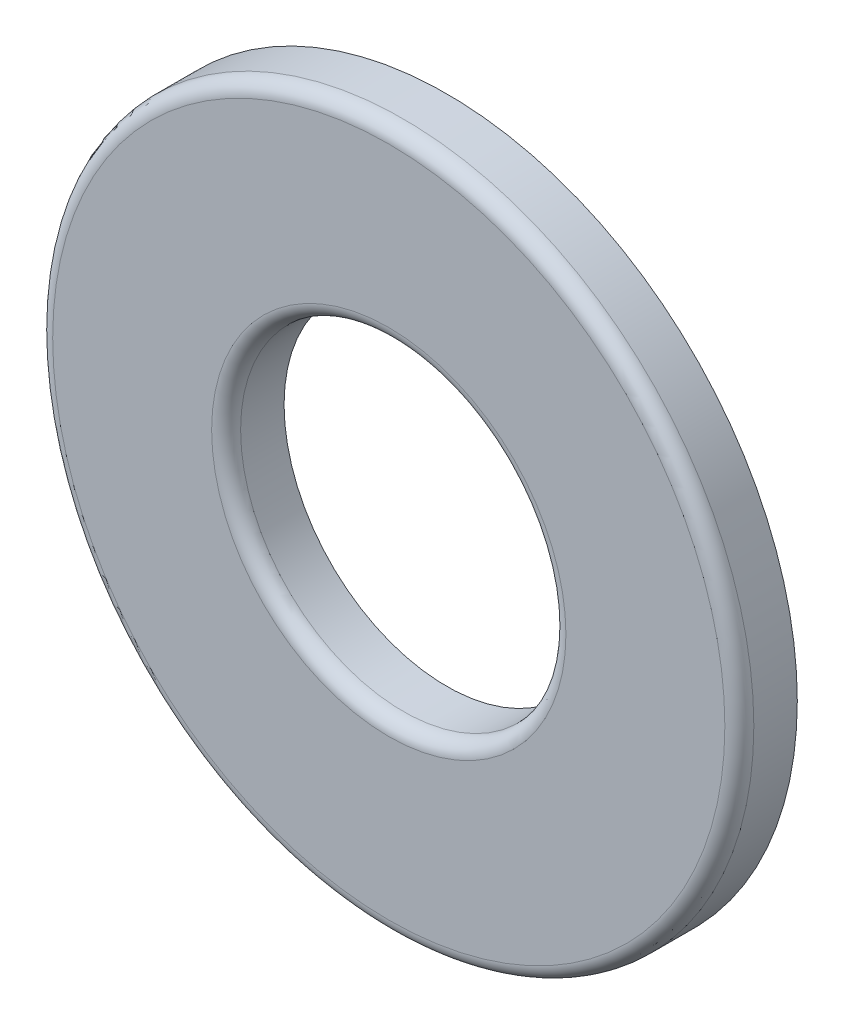
SolidWorks part; units mm, degrees
note: '?' marks a value the reader was unsure of.
other "Imported1" parameters "D1"=0.1968, "TH"=1.0287, "Thickness"=0.7874
ref_plane "Front Plane" through (0, 0, 0) normal (0, 0, 1) x (1, 0, 0)
ref_plane "Top Plane" through (0, 0, 0) normal (0, 1, 0) x (1, 0, 0)
ref_plane "Right Plane" through (0, 0, 0) normal (1, 0, 0) x (0, 0, -1)
sketch "Sketch1" plane through (0, 0, 0) normal (0, 0, 1) x (1, 0, 0)
  line L0 (-4.7625, 0) -> (4.7625, 0) construction
  line L1 (-2.2098, 0) -> (2.2098, 0) construction
  circle A0 centre (0, 0) radius 2.2098 construction
  circle A1 centre (0, 0) radius 4.7625 construction
  point P8 (0, 0)
  point P9 (0, 4.7625)
  point P11 (2.2098, 0)
  dimension "ID" = 4.4196
  dimension "OD" = 9.525
sketch "Sketch2" plane through (0, 0, 0) normal (1, 0, 0) x (0, 0, -1)
  line L0 (-0.3937, 4.7625) -> (0.3937, 4.7625) construction
  point P2 (0, 4.7625)
sketch "Sketch3" plane through (0, 0, 0) normal (0, 0, 1) x (1, 0, 0)
  circle A0 centre (0, 0) radius 2.2098
  circle A1 centre (0, 0) radius 4.7625
extrude "Boss-Extrude1" add sketch "Sketch3" along normal up to vertex (0.3937 mm away) and the other way up to vertex (0.3937 mm away) up to point (0, 4.7625, 0.3937) other way up to point (0, 4.7625, -0.3937)
fillet "Fillet1" radius 0.1968 2 edges at (4.7625, 0, 0.3937) (2.2098, 0, 0.3937)
ref_axis "Center Axis 1" through (0, 0, 0.1968) along (0, 0, -1)?
equation "\"D1@Fillet1\"=\"Thickness@Sketch2\"/4"
